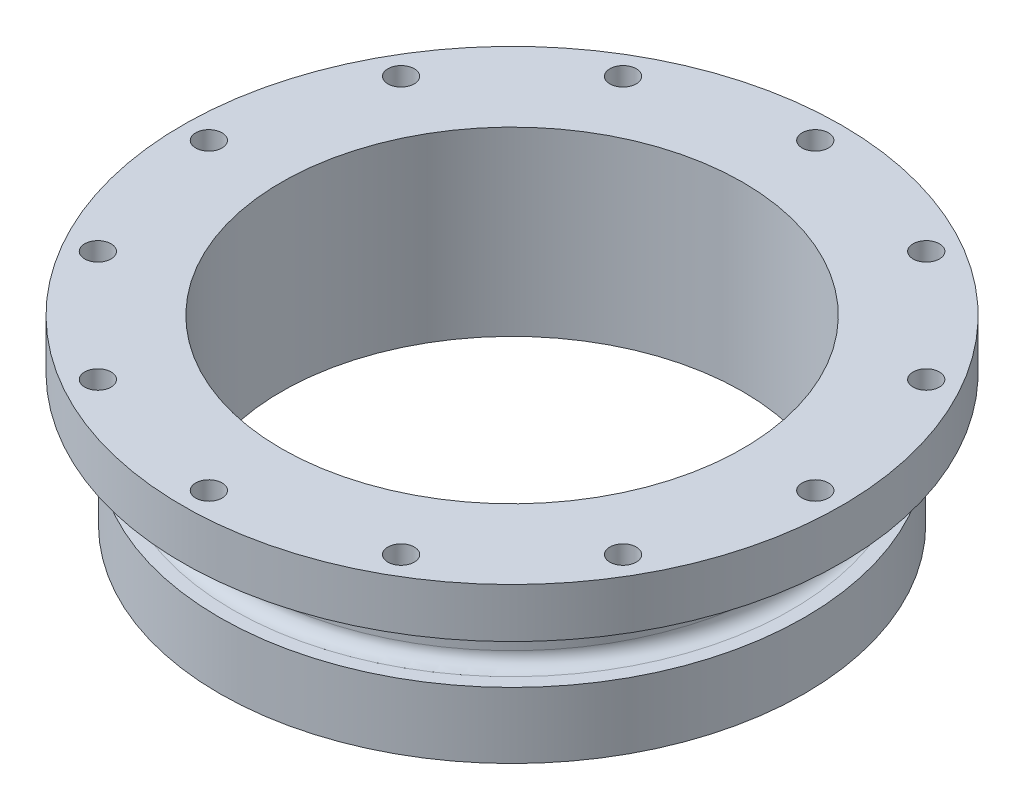
SolidWorks part; units mm, degrees
ref_plane "Front Plane" through (0, 0, 0) normal (0, 0, 1) x (1, 0, 0)
ref_plane "Top Plane" through (0, 0, 0) normal (0, 1, 0) x (1, 0, 0)
ref_plane "Right Plane" through (0, 0, 0) normal (1, 0, 0) x (0, 0, -1)
sketch "Sketch2" plane through (0, 0, 0) normal (0, 1, 0) x (1, 0, 0)
  circle A0 centre (0, 0) radius 56.3562
  dimension "D1" = 112.7125
extrude "Boss-Extrude1" add sketch "Sketch2" along normal blind 25.4
sketch "Sketch3" plane through (0, 25.4, 0) normal (0, 1, 0) x (1, 0, 0)
  circle A0 centre (0, 0) radius 63.5
extrude "Boss-Extrude2" add sketch "Sketch3" along normal blind 9.525
sketch "Sketch4" plane through (0, 0, 0) normal (0, -1, 0) x (1, 0, 0)
  circle A0 centre (0, 0) radius 44.45
extrude "Cut-Extrude1" cut sketch "Sketch4" against normal through all contours A0
sketch "Sketch9" plane through (0, 0, 0) normal (1, 0, 0) x (0, 0, -1)
  line L0 (-63.5, 25.4) -> (63.5, 25.4) construction
  line L1 (56.3562, 25.4) -> (51.2762, 25.4)
  line L2 (56.3562, 25.4) -> (56.3562, 12.7)
  line L3 (56.3562, 12.7) -> (51.2762, 12.7)
  line L4 (51.2762, 25.4) -> (51.2762, 12.7)
  line L5 (-56.3562, 25.4) -> (56.3562, 25.4) construction
  line L6 (0, 0) -> (0, 52.7802) construction
  dimension "D1" = 5.08
  dimension "D2" = 12.7
revolve "Cut-Revolve1" cut sketch "Sketch9" angle 360 about L6
fillet "Fillet1" radius 2.54 2 edges at (0, 12.7, -51.2762) (0, 25.4, -51.2762)
sketch "Sketch10" plane through (0, 25.4, 0) normal (0, -1, 0) x (1, 0, 0)
  circle A0 centre (58.42, 0) radius 2.54
  circle A1 centre (50.5932, -29.21) radius 2.54
  circle A2 centre (29.21, -50.5932) radius 2.54
  circle A3 centre (0, -58.42) radius 2.54
  circle A4 centre (-29.21, -50.5932) radius 2.54
  circle A5 centre (-50.5932, -29.21) radius 2.54
  circle A6 centre (-58.42, 0) radius 2.54
  circle A7 centre (-50.5932, 29.21) radius 2.54
  circle A8 centre (-29.21, 50.5932) radius 2.54
  circle A9 centre (0, 58.42) radius 2.54
  circle A10 centre (29.21, 50.5932) radius 2.54
  circle A11 centre (50.5932, 29.21) radius 2.54
  dimension "D1" = 58.42
  dimension "D3" = 5.08
  dimension "D2" = 12
extrude "Cut-Extrude2" cut sketch "Sketch10" against normal through all
sketch "Sketch11" plane through (0, 0, 0) normal (0, -1, 0) x (1, 0, 0)
  circle A0 centre (51.6255, 0) radius 2.032
  circle A1 centre (44.709, -25.8128) radius 2.032
  circle A2 centre (25.8127, -44.709) radius 2.032
  circle A3 centre (0, -51.6255) radius 2.032
  circle A4 centre (-25.8128, -44.709) radius 2.032
  circle A5 centre (-44.709, -25.8127) radius 2.032
  circle A6 centre (-51.6255, 0) radius 2.032
  circle A7 centre (-44.709, 25.8128) radius 2.032
  circle A8 centre (-25.8127, 44.709) radius 2.032
  circle A9 centre (0, 51.6255) radius 2.032
  circle A10 centre (25.8128, 44.709) radius 2.032
  circle A11 centre (44.709, 25.8127) radius 2.032
  dimension "D2" = 4.064
  dimension "D1" = 51.6255
  dimension "D3" = 12
extrude "Cut-Extrude3" cut sketch "Sketch11" against normal blind 8.89
